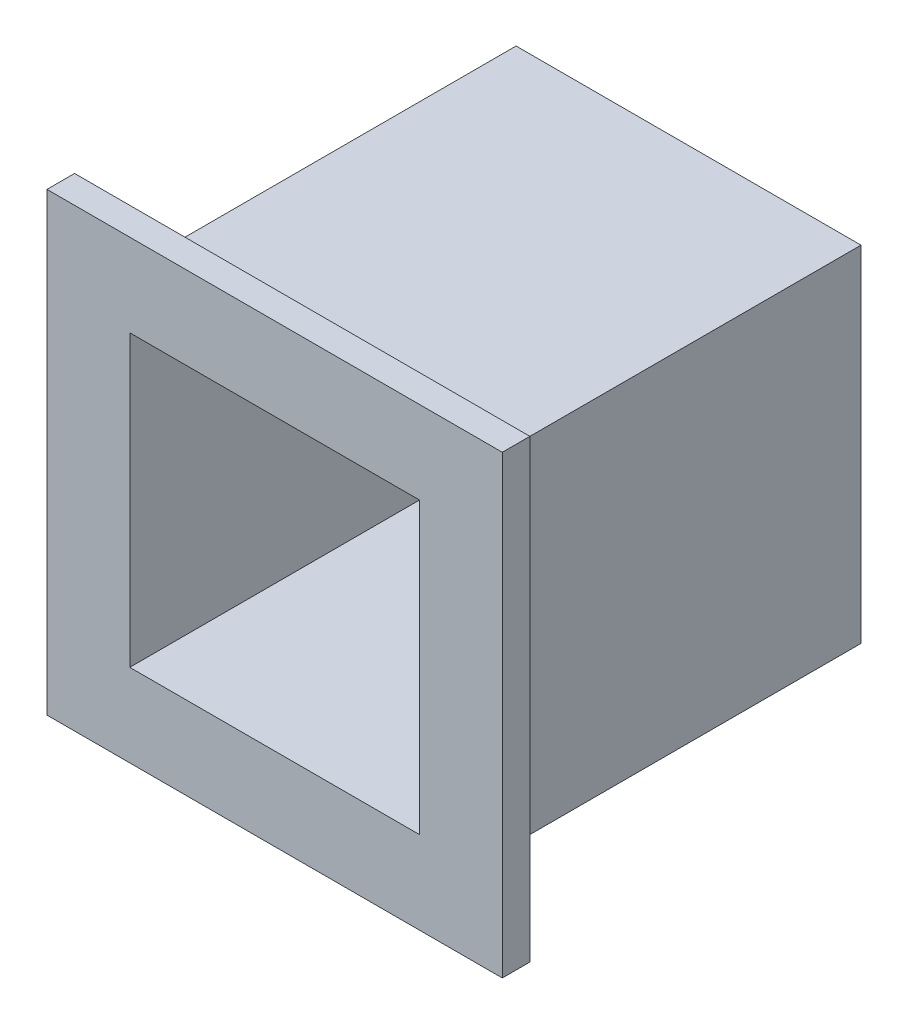
SolidWorks part; units mm, degrees
ref_plane "Front Plane" through (0, 0, 0) normal (0, 0, 1) x (1, 0, 0)
ref_plane "Top Plane" through (0, 0, 0) normal (0, 1, 0) x (1, 0, 0)
ref_plane "Right Plane" through (0, 0, 0) normal (1, 0, 0) x (0, 0, -1)
sketch "Sketch1" plane through (0, 0, 0) normal (0, 0, 1) x (1, 0, 0)
  line L1 (6.25, -6.25) -> (-6.25, -6.25)
  line L2 (6.25, -6.25) -> (6.25, 6.25)
  line L3 (6.25, 6.25) -> (-6.25, 6.25)
  line L4 (-6.25, -6.25) -> (-6.25, 6.25)
  line L5 (6.25, -6.25) -> (-6.25, 6.25) construction
  line L6 (6.25, 6.25) -> (-6.25, -6.25) construction
  point P0 (0, 0)
  dimension "D1" = 12.5
  dimension "D2" = 12.5
extrude "Boss-Extrude1" add sketch "Sketch1" along normal blind 15
shell "Shell3" thickness 1 removed face at (0, 0, 15)
sketch "Sketch2" plane through (0, 0, 15) normal (0, 0, 1) x (1, 0, 0)
  line L0 (8.25, 8.25) -> (-8.25, 8.25)
  line L1 (-8.25, 8.25) -> (-8.25, -8.25)
  line L2 (-8.25, -8.25) -> (8.25, -8.25)
  line L3 (8.25, -8.25) -> (8.25, 8.25)
  line L4 (-6.25, 6.25) -> (-6.25, -6.25)
  line L5 (-6.25, -6.25) -> (6.25, -6.25)
  line L6 (6.25, -6.25) -> (6.25, 6.25)
  line L7 (6.25, 6.25) -> (-6.25, 6.25)
  line L8 (-6.25, 6.25) -> (-6.25, -6.25)
  line L9 (-6.25, -6.25) -> (6.25, -6.25)
  line L10 (6.25, -6.25) -> (6.25, 6.25)
  line L11 (6.25, 6.25) -> (-6.25, 6.25)
  dimension "D1" = 0
  dimension "D2" = 2
extrude "Boss-Extrude2" add sketch "Sketch2" against normal blind 1
